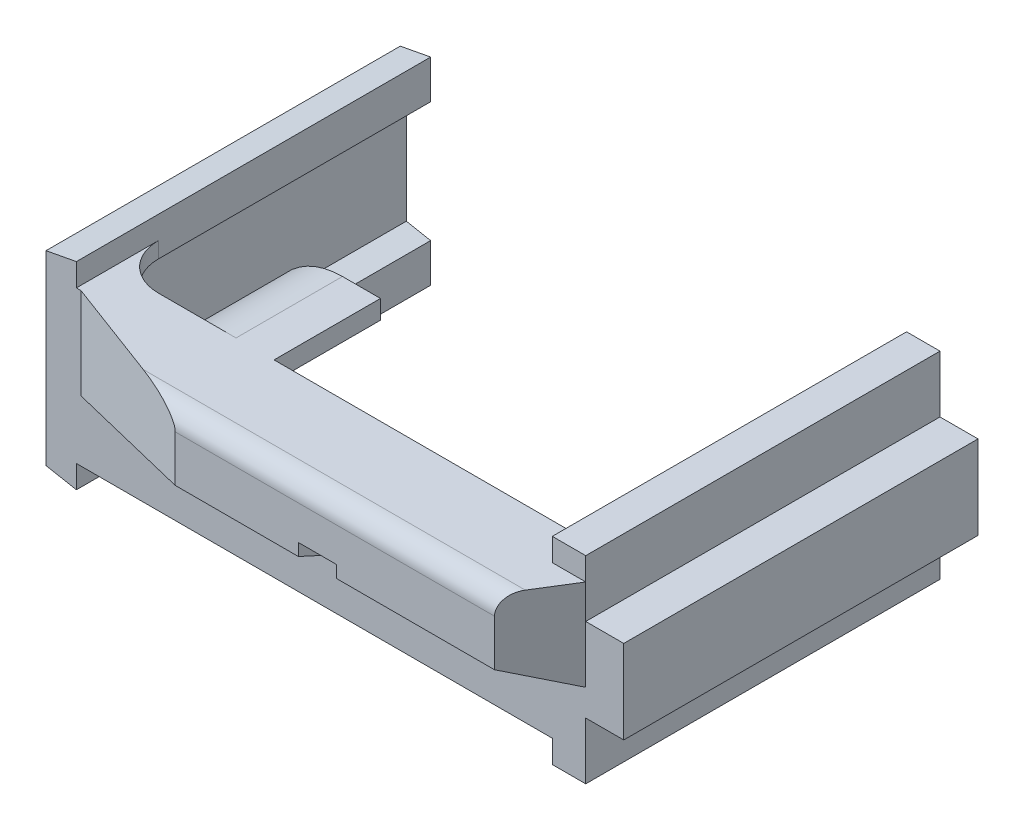
SolidWorks part; units mm, degrees
ref_plane "Front Plane" through (0, 0, 0) normal (0, 0, 1) x (1, 0, 0)
ref_plane "Top Plane" through (0, 0, 0) normal (0, 1, 0) x (1, 0, 0)
ref_plane "Right Plane" through (0, 0, 0) normal (1, 0, 0) x (0, 0, -1)
sketch "Sketch1" plane through (0, 0, 0) normal (0, 0, 1) x (1, 0, 0)
  line L0 (0, 0) -> (57.658, 0) construction
  line L1 (9.398, 6.35) -> (9.398, -6.35)
  line L3 (9.398, 6.35) -> (9.398, 7.7745)
  line L4 (9.398, 7.7745) -> (11.938, 8.255)
  line L5 (11.938, 8.255) -> (11.938, 6.35)
  line L6 (11.938, 6.35) -> (51.689, 6.35)
  line L7 (51.689, 6.35) -> (51.689, 8.255)
  line L8 (51.689, 8.255) -> (54.483, 8.255)
  line L9 (57.658, -3.4925) -> (57.658, 3.4925)
  line L10 (57.658, 3.4925) -> (54.483, 3.4925)
  line L11 (54.483, 3.4925) -> (54.483, 8.255)
  line L12 (54.483, -3.4925) -> (54.483, -8.255)
  line L13 (57.658, -3.4925) -> (54.483, -3.4925)
  line L14 (51.689, -8.255) -> (54.483, -8.255)
  line L15 (51.689, -6.35) -> (51.689, -8.255)
  line L16 (11.938, -6.35) -> (51.689, -6.35)
  line L17 (11.938, -8.255) -> (11.938, -6.35)
  line L18 (9.398, -7.7745) -> (11.938, -8.255)
  line L19 (9.398, -6.35) -> (9.398, -7.7745)
  point P25 (6.604, 0)
  dimension "D1" = 45.085
  dimension "D2" = 16.51
  dimension "D4" = 12.7
  dimension "D5" = 2.54
  dimension "D6" = 2.794
  dimension "D7" = 6.985
  dimension "D8" = 3.175
extrude "Boss-Extrude1" add sketch "Sketch1" against normal blind 34.29
sketch "Sketch2" plane through (9.398, 0, 0) normal (-1, 0, 0) x (0, 0, 1)
  line L0 (-4.699, 8.255) -> (-4.699, 6.35)
  line L1 (-34.29, 8.255) -> (0, 8.255) construction
  line L3 (-4.699, 6.35) -> (0, 6.35)
  line L4 (0, 6.35) -> (0, 8.255)
  line L5 (0, 8.255) -> (-4.699, 8.255)
  line L6 (-4.699, -8.255) -> (-4.699, -1.27)
  line L7 (-34.29, -8.255) -> (0, -8.255) construction
  line L8 (-4.699, -1.27) -> (0, 0.889)
  line L9 (0, 0.889) -> (0, -8.255)
  line L10 (0, -8.255) -> (-4.699, -8.255)
  dimension "D1" = 7.62
  dimension "D2" = 4.699
  dimension "D3" = 5.461
extrude "Cut-Extrude1" cut sketch "Sketch2" against normal through all
sketch "Sketch3" plane through (0, 0, 0) normal (0, 0, 1) x (1, 0, 0)
  line L1 (35.179, 1.905) -> (38.354, 1.905)
  line L2 (35.179, 1.905) -> (35.179, -2.667)
  line L3 (35.179, -2.667) -> (38.354, -2.667)
  line L4 (38.354, 1.905) -> (38.354, -2.667)
  line L5 (54.483, 6.35) -> (9.398, 6.35) construction
  line L6 (57.658, 0.889) -> (57.658, 3.4925) construction
  dimension "D1" = 19.304
  dimension "D2" = 3.175
  dimension "D3" = 4.572
  dimension "D4" = 4.445
extrude "Cut-Extrude2" cut sketch "Sketch3" against normal blind 9.779
sketch "Sketch4" plane through (0, -8.255, 0) normal (0, -1, 0) x (1, 0, 0)
  line L0 (51.689, -34.29) -> (51.689, -7.747)
  line L1 (11.938, -34.29) -> (51.689, -34.29) construction
  line L2 (51.689, -7.747) -> (40.767, -7.747)
  line L3 (40.767, -7.747) -> (40.767, -10.668)
  line L4 (39.243, -12.192) -> (34.671, -12.192)
  line L5 (33.147, -10.668) -> (33.147, -7.747)
  line L6 (33.147, -7.747) -> (25.4, -7.747)
  line L7 (25.4, -7.747) -> (25.4, -16.637)
  line L8 (25.4, -16.637) -> (15.875, -16.637)
  line L9 (15.875, -16.637) -> (15.875, -7.747)
  line L10 (15.875, -7.747) -> (15.748, -7.747)
  line L11 (11.938, -34.29) -> (11.938, -4.699) construction
  line L12 (11.938, -11.557) -> (11.938, -34.29)
  line L13 (11.938, -34.29) -> (51.689, -34.29)
  line L15 (11.938, -4.699) -> (51.689, -4.699) construction
  line L16 (35.179, -9.779) -> (35.179, 0) construction
  line L17 (35.179, -7.747) -> (38.354, -7.747)
  line L18 (35.179, -7.747) -> (35.179, -9.525)
  line L19 (35.941, -10.287) -> (37.592, -10.287)
  line L20 (38.354, -7.747) -> (38.354, -9.525)
  line L21 (57.658, -34.29) -> (57.658, -4.699) construction
  line L22 (57.658, -4.699) -> (54.483, -4.699)
  line L23 (57.658, -4.699) -> (38.354, -4.699) construction
  line L24 (54.483, -4.699) -> (51.562, 0)
  line L25 (57.658, 0) -> (38.354, 0) construction
  line L26 (51.562, 0) -> (57.658, 0)
  line L27 (57.658, 0) -> (57.658, -4.699)
  line L29 (6.604, -4.699) -> (12.319, -4.699)
  line L30 (12.319, -4.699) -> (24.892, 0)
  line L31 (35.179, 0) -> (9.398, 0) construction
  line L32 (24.892, 0) -> (6.604, 0)
  line L33 (6.604, 0) -> (6.604, -4.699)
  arc A0 (40.767, -10.668) -> (39.243, -12.192) centre (39.243, -10.668) cw
  arc A1 (34.671, -12.192) -> (33.147, -10.668) centre (34.671, -10.668) cw
  arc A2 (37.592, -10.287) -> (38.354, -9.525) centre (37.592, -9.525) ccw
  arc A3 (35.179, -9.525) -> (35.941, -10.287) centre (35.941, -9.525) ccw
  arc A4 (15.748, -7.747) -> (11.938, -11.557) centre (15.748, -11.557) ccw
  point P29 (40.767, -12.192)
  point P32 (33.147, -12.192)
  point P35 (38.354, -10.287)
  point P40 (11.938, -7.747)
  dimension "D11" = 1.524
  dimension "D12" = 0.762
  dimension "D13" = 3.81
  dimension "D2" = 3.048
  dimension "D3" = 10.922
  dimension "D4" = 7.62
  dimension "D5" = 4.445
  dimension "D6" = 26.289
  dimension "D7" = 9.525
  dimension "D8" = 8.89
  dimension "D9" = 3.175
  dimension "D10" = 2.54
  dimension "D14" = 5.969
  dimension "D15" = 6.096
  dimension "D16" = 18.288
  dimension "D17" = 5.715
extrude "Cut-Extrude3" cut sketch "Sketch4" against normal through all
sketch "Sketch5" plane through (0, 0, -34.29) normal (0, 0, -1) x (-1, 0, 0)
  line L0 (-33.147, 6.35) -> (-33.147, -6.35) construction
  line L1 (-22.225, -6.35) -> (-15.875, -6.35)
  line L2 (-22.225, 4.7752) -> (-25.4, 4.7752)
  line L3 (-22.225, -4.7752) -> (-25.4, -4.7752)
  line L4 (-25.4, 4.7752) -> (-25.4, -4.7752)
  line L5 (-40.767, 6.35) -> (-33.147, 6.35)
  line L7 (-9.906, 4.6366) -> (-11.938, 5.021)
  line L8 (-11.938, -8.255) -> (-11.938, 8.255) construction
  line L15 (-9.906, -4.6366) -> (-11.938, -5.021)
  line L16 (-11.938, 5.021) -> (-15.875, 5.021)
  line L17 (-9.906, 4.6366) -> (-9.906, -4.6366)
  line L18 (-57.658, 0) -> (0, 0) construction
  line L21 (-15.875, 6.35) -> (-15.875, -6.35) construction
  line L22 (-22.225, 6.35) -> (-15.875, 6.35)
  line L23 (-15.875, 6.35) -> (-15.875, 5.021)
  line L24 (-15.875, -5.021) -> (-15.875, -6.35)
  line L25 (-11.938, -5.021) -> (-15.875, -5.021)
  line L26 (-22.225, -6.35) -> (-25.4, -6.35) construction
  line L27 (-22.225, 6.35) -> (-25.4, 6.35) construction
  line L28 (-40.767, 6.35) -> (-40.767, 1.5875)
  line L29 (-40.767, 1.5875) -> (-33.147, 1.5875)
  line L30 (-33.147, 6.35) -> (-33.147, 1.5875)
  line L31 (-33.147, -6.35) -> (-33.147, -1.5875)
  line L32 (-40.767, -1.5875) -> (-33.147, -1.5875)
  line L33 (-40.767, -6.35) -> (-40.767, -1.5875)
  line L34 (-40.767, -6.35) -> (-33.147, -6.35)
  line L35 (-55.753, -1.397) -> (-55.753, 1.397)
  line L36 (-55.753, 1.397) -> (-54.182, 1.397)
  line L37 (-54.182, 1.397) -> (-51.689, 5.715)
  line L38 (-51.689, 6.35) -> (-51.689, -6.35) construction
  line L40 (-57.658, -3.4925) -> (-57.658, 3.4925) construction
  line L41 (-54.483, 8.255) -> (-51.689, 8.255) construction
  line L42 (-51.689, 5.715) -> (-51.689, -5.715)
  line L43 (-54.182, -1.397) -> (-51.689, -5.715)
  line L44 (-55.753, -1.397) -> (-54.182, -1.397)
  arc A0 (-22.225, -6.35) -> (-22.225, 6.35) centre (-22.225, 0) ccw construction
  arc A1 (-22.225, 6.35) -> (-22.225, -6.35) centre (-22.225, 0) cw
  arc A2 (-22.225, 4.7752) -> (-22.225, -4.7752) centre (-22.225, 0) cw
  arc A3 (-25.4, 5.4993) -> (-25.4, -5.4993) centre (-22.225, 0) ccw construction
  point P27 (-51.689, 0)
  point P61 (-55.753, 0)
  line M5 (-11.938, 8.255) -> (-11.938, -8.255)
  dimension "D4" = 12.7
  dimension "D5" = 1.5748
  dimension "D6" = 9.525
  dimension "D7" = 9.5504
  dimension "D8" = 4.7625
  dimension "D9" = 2.54
  dimension "D10" = 2.794
  dimension "D11" = 1.905
  dimension "D12" = 30
extrude "Cut-Extrude4" cut sketch "Sketch5" against normal up to surface (26.543 mm away) contours L30 L5 L28 L29 | L33 L34 L31 L32 | A2 L2 L4 L3 | L22 A1 L23 | L24 A1 L1 | L17 L7 L15 M5 | L35 L44 L43 L42 L37 L36 region at (14.9377, 0, -34.29) region at (10.9355, 0, -34.29) region at (21.8553, 0, -34.29) region at (36.957, 3.9687, -34.29) region at (36.957, -3.9687, -34.29) region at (53.1365, 0, -34.29) up to face at (29.2735, 0, -7.747)
fillet "Fillet4" radius 1.5875 1 edges at (38.227, 6.35, 0) tangent propagation no
